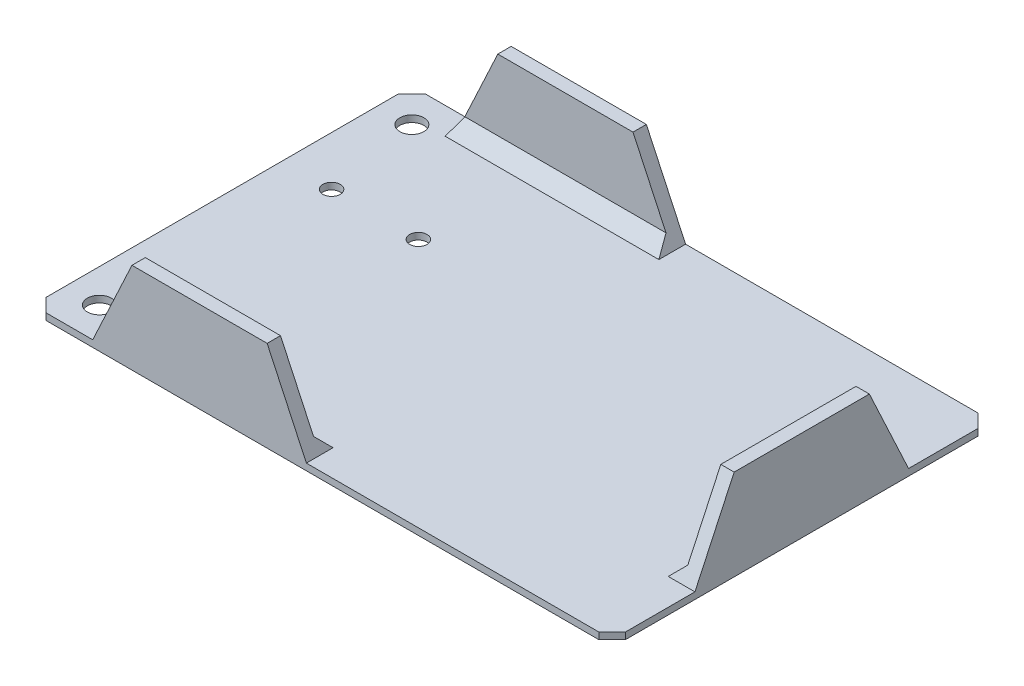
SolidWorks part; units mm, degrees
ref_plane "Front Plane" through (0, 0, 0) normal (0, 0, 1) x (1, 0, 0)
ref_plane "Top Plane" through (0, 0, 0) normal (0, 1, 0) x (1, 0, 0)
ref_plane "Right Plane" through (0, 0, 0) normal (1, 0, 0) x (0, 0, -1)
sketch "Sketch1" plane through (0, 0, 0) normal (0, 1, 0) x (1, 0, 0)
  line L1 (0, 0) -> (110.236, 0)
  line L2 (0, 0) -> (0, 72.136)
  line L3 (0, 72.136) -> (110.236, 72.136)
  line L4 (110.236, 0) -> (110.236, 72.136)
  dimension "D1" = 110.236
  dimension "D2" = 72.136
extrude "Boss-Extrude1" add sketch "Sketch1" along normal blind 1.27
sketch "Sketch2" plane through (0, 1.27, 0) normal (0, 1, 0) x (1, 0, 0)
  line L0 (110.236, 0) -> (110.236, 72.136) construction
  line L1 (35.236, 64.568) -> (97.536, 64.568) construction
  line L2 (35.236, 64.568) -> (35.236, 7.568) construction
  line L3 (35.236, 7.568) -> (97.536, 7.568) construction
  line L4 (97.536, 64.568) -> (97.536, 7.568) construction
  line L5 (110.236, 72.136) -> (0, 72.136) construction
  line L6 (0, 72.136) -> (0, 0) construction
  line L8 (9.363, 47.498) -> (25.873, 47.498) construction
  line L9 (6.823, 50.038) -> (28.413, 50.038) construction
  line L10 (6.823, 50.038) -> (6.823, 22.098) construction
  line L11 (6.823, 22.098) -> (28.413, 22.098) construction
  line L12 (28.413, 50.038) -> (28.413, 22.098) construction
  line L13 (0, 36.068) -> (6.823, 36.068) construction
  line L14 (28.413, 36.068) -> (35.236, 36.068) construction
  line L15 (35.236, 36.068) -> (47.696, 36.068) construction
  line L16 (47.696, 36.068) -> (60.156, 36.068) construction
  line L17 (60.156, 36.068) -> (72.616, 36.068) construction
  line L18 (72.616, 36.068) -> (85.076, 36.068) construction
  line L19 (85.076, 36.068) -> (97.536, 36.068) construction
  circle A0 centre (6.35, 65.786) radius 2.286
  circle A2 centre (9.363, 47.498) radius 1.651
  circle A3 centre (25.873, 47.498) radius 1.651
  circle A6 centre (47.696, 36.068) radius 2.286 construction
  circle A7 centre (60.156, 36.068) radius 2.286 construction
  circle A8 centre (72.616, 36.068) radius 2.286 construction
  circle A9 centre (85.076, 36.068) radius 2.286 construction
  circle A10 centre (6.35, 6.35) radius 2.286
  point P7 (97.536, 36.068)
  point P10 (110.236, 36.068)
  point P22 (6.823, 36.068)
  point P23 (0, 36.068)
  point P28 (17.618, 47.498)
  point P29 (17.618, 50.038)
  dimension "D3" = 4.572
  dimension "D4" = 6.35
  dimension "D5" = 6.35
  dimension "D10" = 3.302
  dimension "D14" = 4.572
  dimension "D1" = 62.3
  dimension "D2" = 57
  dimension "D8" = 27.94
  dimension "D9" = 21.59
  dimension "D11" = 16.51
  dimension "D12" = 2.54
  dimension "D13" = 12.7
extrude "Cut-Extrude1" cut sketch "Sketch2" against normal blind 1.27
sketch "Sketch3" plane through (0, 1.27, 0) normal (0, 1, 0) x (1, 0, 0)
  line L0 (110.236, 72.136) -> (0, 72.136) construction
  line L1 (19.05, 72.136) -> (44.45, 72.136)
  line L2 (19.05, 72.136) -> (19.05, 69.596)
  line L3 (19.05, 69.596) -> (44.45, 69.596)
  line L4 (44.45, 72.136) -> (44.45, 69.596)
  line L5 (0, 0) -> (110.236, 0) construction
  line L6 (44.45, 0) -> (19.05, 0)
  line L7 (44.45, 0) -> (44.45, 2.54)
  line L8 (44.45, 2.54) -> (19.05, 2.54)
  line L9 (19.05, 0) -> (19.05, 2.54)
  line L10 (110.236, 0) -> (110.236, 72.136) construction
  line L11 (110.236, 23.368) -> (107.696, 23.368)
  line L12 (110.236, 23.368) -> (110.236, 48.768)
  line L13 (110.236, 48.768) -> (107.696, 48.768)
  line L14 (107.696, 23.368) -> (107.696, 48.768)
  line L15 (0, 72.136) -> (0, 0) construction
  point P18 (31.75, 69.596)
  point P19 (31.75, 2.54)
  point P20 (107.696, 36.068)
  dimension "D1" = 2.54
  dimension "D2" = 2.54
  dimension "D3" = 2.54
  dimension "D4" = 25.4
  dimension "D5" = 19.05
  dimension "D6" = 25.4
extrude "Boss-Extrude2" add sketch "Sketch3" along normal blind 16
chamfer "Chamfer1" distance 7.62 angle 65 6 edges at (44.45, 1.27, -1.27) (44.45, 1.27, -70.866) (19.05, 1.27, -1.27) (19.05, 1.27, -70.866) (108.966, 1.27, -48.768) (108.966, 1.27, -23.368) first distance on face at (25.873, 1.27, -45.847)
chamfer "Chamfer2" distance 2.54 angle 45 3 edges at (31.75, 1.27, -2.54) (31.75, 1.27, -69.596) (107.696, 1.27, -36.068)
chamfer "Chamfer3" distance 2.54 angle 45 4 edges at (110.236, 0.635, 0) (110.236, 0.635, -72.136) (0, 0.635, -72.136) (0, 0.635, 0)
